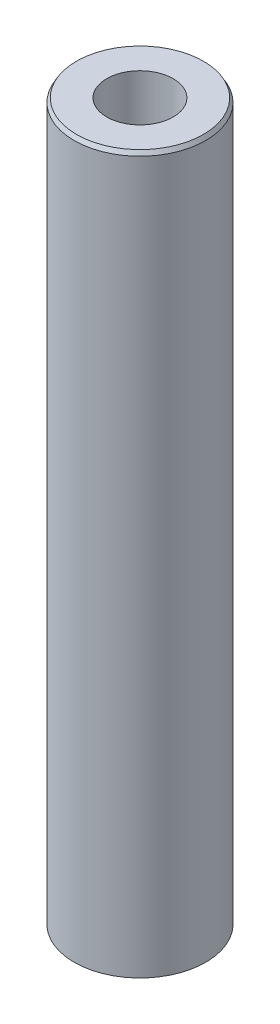
SolidWorks part; units mm, degrees
ref_plane "Front Plane" through (0, 0, 0) normal (0, 0, 1) x (1, 0, 0)
ref_plane "Top Plane" through (0, 0, 0) normal (0, 1, 0) x (1, 0, 0)
ref_plane "Right Plane" through (0, 0, 0) normal (1, 0, 0) x (0, 0, -1)
sketch "Sketch1" plane through (0, 0, 0) normal (0, 1, 0) x (1, 0, 0)
  circle A0 centre (0, 0) radius 55
  dimension "SHAFT_OD" = 110
extrude "Boss-Extrude1" add sketch "Sketch1" along normal blind 600
sketch "Sketch2" plane through (0, 0, 0) normal (0, 1, 0) x (1, 0, 0)
  circle A0 centre (0, 0) radius 27.7656
  dimension "BORE_D" = 55.5311
extrude "Cut-Extrude1" cut sketch "Sketch2" along normal through all
chamfer "Chamfer1" distance 3.4104 angle 30 2 edges at (0, 600, 55) (0, 0, 55) first distance on face at (0, 600, 55) first distance on face at (0, 0, 27.7656)
